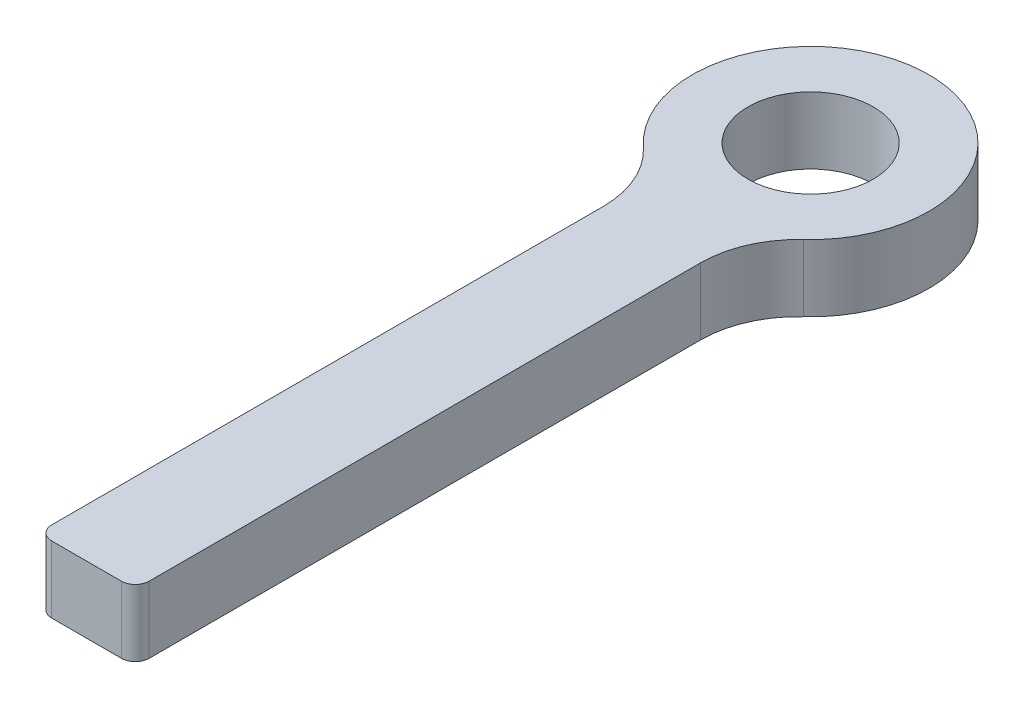
SolidWorks part; units mm, degrees
material "AISI 1020"
ref_plane "Plano frontal" through (0, 0, 0) normal (0, 0, 1) x (1, 0, 0)
ref_plane "Plano superior" through (0, 0, 0) normal (0, 1, 0) x (1, 0, 0)
ref_plane "Plano direito" through (0, 0, 0) normal (1, 0, 0) x (0, 0, -1)
sketch "Esboço1" plane through (0, 0, 0) normal (0, 1, 0) x (1, 0, 0)
  line L0 (0, 0) -> (0, 52) construction
  line L1 (-3.5, 40.5982) -> (-3.5, 1)
  line L2 (-2.5, 0) -> (2.5, 0)
  line L3 (3.5, 1) -> (3.5, 40.5982)
  circle A0 centre (0, 52) radius 4.5
  arc A1 (5.7581, 45.7474) -> (-5.7581, 45.7474) centre (0, 52) ccw
  arc A2 (-3.5, 40.5982) -> (-5.7581, 45.7474) centre (-10.5, 40.5982) ccw
  arc A3 (3.5, 40.5982) -> (5.7581, 45.7474) centre (10.5, 40.5982) cw
  arc A4 (2.5, 0) -> (3.5, 1) centre (2.5, 1) ccw
  arc A5 (-2.5, 0) -> (-3.5, 1) centre (-2.5, 1) cw
  point P14 (3.5, 0)
  point P17 (-3.5, 0)
  dimension "D3" = 9
  dimension "D4" = 8.5
  dimension "D5" = 7
  dimension "D6" = 1
  dimension "D1" = 7
  dimension "D2" = 52
base flange "Flange-base1" sketch "Esboço1" thickness 4.8 reverse thickness direction no parameters "D1"=0.7366
sketch "Curva-Linhas1" [suppressed] plane through (0, 0, 0) normal (0, 1, 0) x (1, 0, 0)
sketch "Caixa delimitadora1" [suppressed] plane through (0, 0, 0) normal (0, 1, 0) x (1, 0, 0)
sheet metal parameters "Chapa metálica1" thickness 4.8 parameters "D1"=0.7366
flat pattern "Padrão-Plano1" [suppressed]
sketch "Curva-Linhas2" plane through (0, 0, 0) normal (0, 1, 0) x (1, 0, 0)
sketch3d "Caixa delimitadora2" [suppressed]
  line L0 (-1.2059, 19.0253, 0) -> (-7.1514, -41.1807, 0) construction
  line L1 (-18.1234, 20.6959, 0) -> (-24.069, -39.51, 0) construction
  line L2 (-1.2059, 19.0253, 0) -> (-18.1234, 20.6959, 0) construction
  line L3 (-7.1514, -41.1807, 0) -> (-24.069, -39.51, 0) construction
